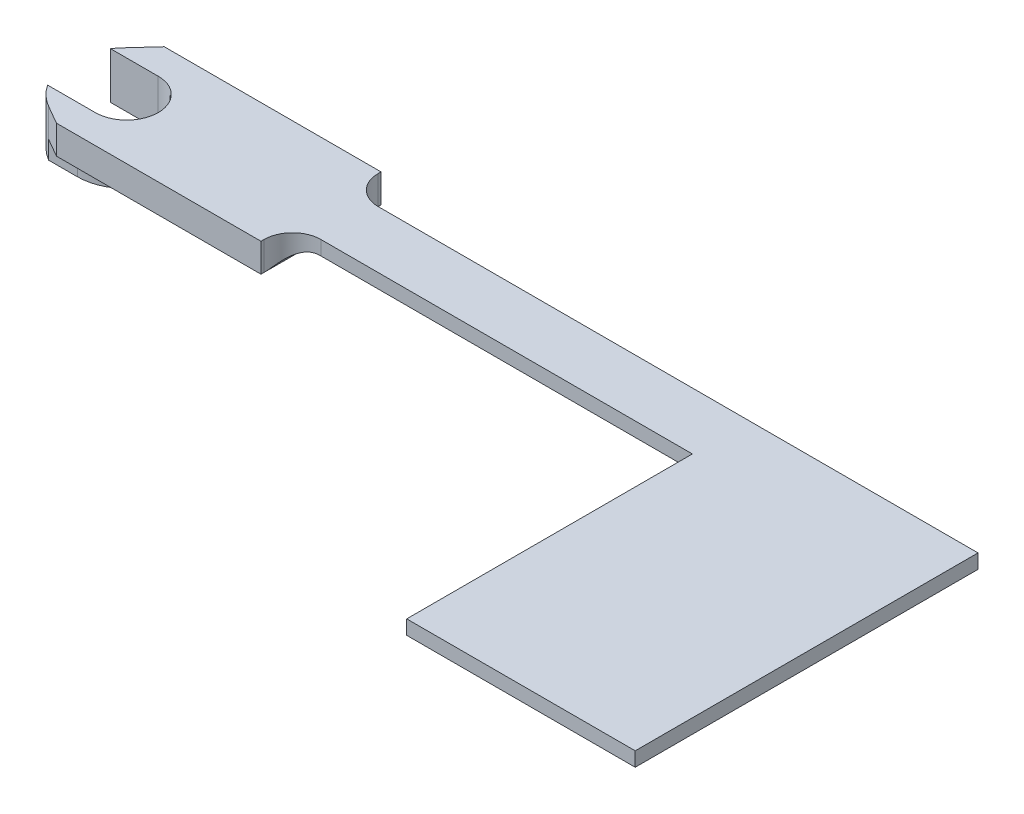
SolidWorks part; units mm, degrees
ref_plane "Front Plane" through (0, 0, 0) normal (0, 0, 1) x (1, 0, 0)
ref_plane "Top Plane" through (0, 0, 0) normal (0, 1, 0) x (1, 0, 0)
ref_plane "Right Plane" through (0, 0, 0) normal (1, 0, 0) x (0, 0, -1)
sketch "Sketch1" plane through (0, 0, 0) normal (0, 1, 0) x (1, 0, 0)
  line L0 (0, 0) -> (27.8118, 30.498) construction
  line L1 (0, 0) -> (41.275, 0) construction
  line L2 (23.296, 15.6137) -> (32.6062, 26.3344)
  line L3 (-4.692, 4.2787) -> (23.1198, 34.7768)
  line L4 (-3.175, -5.4993) -> (27.7812, -23.3719)
  line L5 (41.275, -23.8125) -> (41.275, -26.9875) construction
  line L6 (47.849, -24.5345) -> (47.4381, -23.0011) construction
  line L7 (47.849, -24.5345) -> (48.2599, -26.0679) construction
  circle A4 centre (41.275, 0) radius 19.05 construction
  circle A5 centre (41.275, 0) radius 23.8125
  circle A6 centre (41.275, 0) radius 26.9875
  circle A7 centre (27.8118, 30.498) radius 6.35
  arc A8 (41.275, -26.9875) -> (41.275, -23.8125) centre (41.275, -25.4) ccw construction
  circle A10 centre (0, 0) radius 6.35
  arc A11 (48.2599, -26.0679) -> (47.4381, -23.0011) centre (47.849, -24.5345) ccw
  dimension "D1" = 38.1
  dimension "D4" = 12.7
  dimension "D5" = 3.175
  dimension "D3" = 12.7
  dimension "D6" = 41.275
  dimension "D7" = 15
  dimension "D2" = 4.7625
extrude "Boss-Extrude1" add sketch "Sketch1" along normal blind 4.7625
sketch "Sketch2" plane through (0, 4.7625, 0) normal (0, 1, 0) x (1, 0, 0)
  line L0 (0, 3.5) -> (-5.2983, 3.5)
  line L1 (0, -3.5) -> (-5.2983, -3.5)
  line L2 (1.8028, 3) -> (17.8028, 2)
  line L3 (17.8028, 2) -> (17.8028, -2)
  line L4 (17.8028, -2) -> (1.8028, -3)
  line L5 (1.8028, 3) -> (1.8028, -3) construction
  circle A0 centre (0, 0) radius 3.5
  arc A1 (-4.692, 4.2787) -> (-3.175, -5.4993) centre (0, 0) ccw construction
  arc A2 (-5.2983, 3.5) -> (-5.2983, -3.5) centre (0, 0) ccw
  point P12 (1.8028, 0)
  point P16 (17.8028, 0)
  dimension "D1" = 7
  dimension "D2" = 6
  dimension "D3" = 4
  dimension "D4" = 16
sketch "Sketch5" plane through (0, 0, 0) normal (0, -1, 0) x (1, 0, 0)
  line L0 (0, 3.5) -> (-5.2983, 3.5) construction
  line L1 (0, -3.5) -> (-5.2983, -3.5) construction
  line L2 (0, 3.5) -> (-5.2983, 3.5)
  line L3 (0, -3.5) -> (-5.2983, -3.5)
  circle A0 centre (0, 0) radius 3.5 construction
  circle A1 centre (0, 0) radius 3.5
  arc M1 (-3.175, 5.4993) -> (-4.692, -4.2787) centre (0, 0) ccw
extrude "Cut-Extrude2" cut sketch "Sketch5" against normal offset from surface (3.3712 mm away) 1.3912 contours A1 | A1 L2 L3 M1 up to face at (22.9306, 4.7625, 0.3962)
sketch "Sketch6" plane through (0, 3.3713, 0) normal (0, -1, 0) x (1, 0, 0)
  line L0 (17.8028, -2) -> (17.8028, 2) construction
  line L1 (1.8028, -3) -> (17.8028, -2) construction
  line L2 (17.8028, 2) -> (1.8028, 3) construction
  line L3 (17.8028, -2) -> (17.8028, 2)
  line L4 (1.8028, -3) -> (17.8028, -2)
  line L5 (17.8028, 2) -> (1.8028, 3)
  circle A0 centre (0, 0) radius 3.5 construction
  arc A1 (1.8028, -3) -> (1.8028, 3) centre (0, 0) ccw
extrude "Cut-Extrude3" cut sketch "Sketch6" along normal offset from surface (1.98 mm away) 1.3912 up to face at (14.8799, 0, 0.2432)
sketch "Sketch10" plane through (-3.175, 0, 5.4993) normal (-0.5, 0, 0.866) x (0.866, 0, 0.5)
  line L0 (12.368, 0) -> (15.0706, 0) construction
  line L1 (15.0706, 4.7625) -> (12.368, 4.7625) construction
  line L2 (11.9327, 0) -> (52.5832, 0) construction
  line L3 (52.5832, 4.7625) -> (11.9327, 4.7625) construction
  line L4 (2.6339, 0) -> (15.1867, 0) construction
  line L5 (15.1867, 4.7625) -> (2.6339, 4.7625) construction
  line L6 (2.6339, 0) -> (-6.2028, 0) construction
  line L7 (-6.2028, 4.7625) -> (2.6339, 4.7625) construction
  line L8 (-6.35, 3.3712) -> (-2.8385, 3.3712) construction
  line L9 (-2.8385, 3.3712) -> (-2.8385, 0) construction
  line L10 (-2.8385, 0) -> (0, 0) construction
  line L11 (0, 4.7625) -> (-6.35, 4.7625) construction
  line L12 (-6.3385, 0) -> (-6.2028, 0) construction
  line L13 (-6.3385, 0) -> (-6.3385, 3.3712) construction
  line L14 (0, 0) -> (35.7452, 0) construction
  line L15 (35.7452, 4.7625) -> (0, 4.7625) construction
  line L16 (35.7452, 0) -> (54.8282, 0) construction
  line L17 (54.8282, 4.7625) -> (35.7452, 4.7625) construction
  line L18 (52.5832, 0) -> (55.2932, 0) construction
  line L19 (55.2932, 4.7625) -> (52.5832, 4.7625) construction
  line L20 (12.368, 0) -> (15.0706, 0) construction
  line L21 (15.0706, 4.7625) -> (12.368, 4.7625) construction
  line L22 (11.9327, 0) -> (52.5832, 0) construction
  line L23 (52.5832, 4.7625) -> (11.9327, 4.7625) construction
  line L24 (2.6339, 0) -> (15.1867, 0) construction
  line L25 (15.1867, 4.7625) -> (2.6339, 4.7625) construction
  line L26 (2.6339, 0) -> (-6.2028, 0) construction
  line L27 (-6.2028, 4.7625) -> (2.6339, 4.7625) construction
  line L28 (-6.35, 3.3712) -> (-2.8385, 3.3712) construction
  line L29 (-2.8385, 3.3712) -> (-2.8385, 0) construction
  line L30 (-2.8385, 0) -> (0, 0) construction
  line L31 (0, 4.7625) -> (-6.35, 4.7625) construction
  line L32 (-6.3385, 0) -> (-6.2028, 0) construction
  line L33 (-6.3385, 0) -> (-6.3385, 3.3712) construction
  line L34 (0, 0) -> (35.7452, 0) construction
  line L35 (35.7452, 4.7625) -> (0, 4.7625) construction
  line L36 (35.7452, 0) -> (54.8282, 0) construction
  line L37 (54.8282, 4.7625) -> (35.7452, 4.7625) construction
  line L38 (52.5832, 0) -> (55.2932, 0) construction
  line L39 (55.2932, 4.7625) -> (52.5832, 4.7625) construction
  line L41 (-6.35, 4.7625) -> (55.2932, 4.7625)
  line L42 (-6.35, 4.7625) -> (-6.35, 0)
  line L43 (-6.35, 0) -> (55.2932, 0)
  line L44 (55.2932, 4.7625) -> (55.2932, 0)
  line L45 (-6.35, 3.9688) -> (55.2932, 3.9688)
  line L46 (-6.35, 3.9688) -> (-6.35, 0.7938)
  line L47 (-6.35, 0.7938) -> (55.2932, 0.7938)
  line L48 (55.2932, 3.9688) -> (55.2932, 0.7938)
  point P26 (-6.35, 2.3813)
  line M29 (0, 0) -> (35.7452, 0)
  line M30 (35.7452, 0) -> (35.7452, 4.7625)
  line M31 (35.7452, 4.7625) -> (0, 4.7625)
  line M32 (0, 4.7625) -> (0, 0)
  dimension "D1" = 3.175
  dimension "D2" = 1.5875
extrude "Cut-Extrude4" cut sketch "Sketch10" against normal through all contours L42 L45 L41 M32 | L45 M32 M30 M31 | L45 L44 L41 M30 | L47 L43 L44 M30 | L47 M32 M29 M30 | L47 L42 L43 M32
sketch "Sketch11" plane through (0, 3.3713, 0) normal (0, -1, 0) x (1, 0, 0)
  line L0 (-5.2983, 3.5) -> (0, 3.5) construction
  line L1 (-5.2983, -3.5) -> (0, -3.5) construction
  line L2 (-5.2983, 3.5) -> (0, 3.5)
  line L3 (-5.2983, -3.5) -> (0, -3.5)
  arc A0 (-5.2983, 3.5) -> (-5.2983, -3.5) centre (0, 0) ccw construction
  arc A1 (0, -3.5) -> (0, 3.5) centre (0, 0) ccw construction
  arc A2 (-5.2983, 3.5) -> (-5.2983, -3.5) centre (0, 0) ccw
  arc A3 (0, -3.5) -> (0, 3.5) centre (0, 0) ccw
extrude "Cut-Extrude5" cut sketch "Sketch11" against normal blind 2.54
sketch "Sketch12" plane through (0, 0.7938, 0) normal (0, -1, 0) x (1, 0, 0)
  line L0 (-3.175, 5.4993) -> (27.7812, 23.3719) construction
  line L1 (23.1198, -34.7768) -> (-4.692, -4.2787) construction
  line L2 (-5.2983, 3.5) -> (0, 3.5) construction
  line L3 (-5.2983, -3.5) -> (0, -3.5) construction
  line L4 (-3.175, 5.4993) -> (-3.1737, 5.5)
  line L5 (-3.5783, -5.5) -> (-4.692, -4.2787)
  line L6 (-5.2983, 3.5) -> (0, 3.5)
  line L7 (-5.2983, -3.5) -> (0, -3.5)
  line L8 (-3.5783, -5.5) -> (0, -5.5)
  line L9 (-3.1737, 5.5) -> (0, 5.5)
  line L10 (-5.2983, -5.5) -> (0, -5.5) construction
  line L11 (-5.2983, 5.5) -> (0, 5.5) construction
  arc A0 (-5.2983, -3.5) -> (-4.692, -4.2787) centre (0, 0) ccw construction
  arc A1 (-3.175, 5.4993) -> (-5.2983, 3.5) centre (0, 0) ccw construction
  arc A2 (0, -3.5) -> (0, 3.5) centre (0, 0) ccw construction
  arc A3 (-5.2983, -3.5) -> (-4.692, -4.2787) centre (0, 0) ccw
  arc A4 (-3.175, 5.4993) -> (-5.2983, 3.5) centre (0, 0) ccw
  arc A5 (0, -3.5) -> (0, 3.5) centre (0, 0) ccw
  arc A6 (0, -5.5) -> (0, 5.5) centre (0, 0) ccw
  dimension "D1" = 2
extrude "Boss-Extrude2" add sketch "Sketch12" along normal blind 2
sketch "Sketch14" plane through (0, 3.9688, 0) normal (0, 1, 0) x (1, 0, 0)
  line L0 (0, -3.5) -> (-5.2983, -3.5) construction
  line L1 (-5.2983, 3.5) -> (17.7211, 3.5)
  line L2 (1.8028, -3) -> (17.548, -2.0159)
  line L3 (17.548, 2.0159) -> (1.8028, 3)
  line L4 (1.8028, -3) -> (17.548, -2.0159)
  line L5 (17.548, 2.0159) -> (1.8028, 3)
  line L6 (-5.2983, 3.5) -> (-5.2983, -3.5)
  line L7 (-5.2983, -3.5) -> (17.7211, -3.5)
  line L8 (17.7211, 3.5) -> (17.7211, -3.5)
  line L9 (-8.4733, 6.675) -> (20.8961, 6.675)
  line L10 (20.8961, 6.675) -> (20.8961, -6.675)
  line L11 (-8.4733, -6.675) -> (20.8961, -6.675)
  line L12 (-8.4733, 6.675) -> (-8.4733, -6.675)
  line L13 (-5.2983, 3.5) -> (-5.2983, 6.675)
  line L14 (-5.2983, -3.5) -> (-5.2983, -6.675)
  arc A0 (23.296, 15.6137) -> (47.4381, -23.0011) centre (41.275, 0) ccw construction
  arc A1 (23.296, 15.6137) -> (47.4381, -23.0011) centre (41.275, 0) ccw
  arc A2 (1.8028, -3) -> (1.8028, 3) centre (0, 0) ccw
  arc A3 (17.548, 2.0159) -> (17.548, -2.0159) centre (41.275, 0) ccw
  arc A4 (1.8028, -3) -> (1.8028, 3) centre (0, 0) ccw
  arc A5 (17.548, 2.0159) -> (17.548, -2.0159) centre (41.275, 0) ccw
  line M16 (-3.175, -5.4993) -> (27.7812, -23.3719)
  arc M17 (27.7812, -23.3719) -> (48.2599, -26.0679) centre (41.275, 0) ccw
  arc M18 (48.2599, -26.0679) -> (47.4381, -23.0011) centre (47.849, -24.5345) ccw
  arc M19 (47.4381, -23.0011) -> (23.296, 15.6137) centre (41.275, 0) cw
  line M20 (23.296, 15.6137) -> (32.6062, 26.3344)
  arc M21 (32.6062, 26.3344) -> (23.1198, 34.7768) centre (27.8118, 30.498) ccw
  line M22 (23.1198, 34.7768) -> (-4.692, 4.2787)
  dimension "D1" = 0
  dimension "D2" = 3.175
extrude "Cut-Extrude6" cut sketch "Sketch14" against normal through all contours L9 M22 M19 M20 M21 | L11 M16 M17 M18 M19
ref_plane "Plane1" through (18.4172, 0, 0) normal (1, 0, 0) x (0, 0, -1)
sketch "Sketch15" plane through (18.4172, 0, 0) normal (1, 0, 0) x (0, 0, -1)
  line L0 (2.0159, 1.3913) -> (-2.0159, 1.3913) construction
  line L1 (-2.0159, 1.3913) -> (-2.0159, 3.3713) construction
  line L2 (-2.0159, 3.3713) -> (2.0159, 3.3713) construction
  line L3 (2.0159, 3.3713) -> (2.0159, 1.3913) construction
  line L4 (6.675, 0.7938) -> (6.675, 3.9688)
  line L5 (6.675, 3.9688) -> (-6.675, 3.9688)
  line L6 (-6.675, 3.9688) -> (-6.675, 0.7938)
  line L7 (-6.675, 0.7938) -> (6.675, 0.7938)
  line L8 (6.675, 0.7938) -> (6.675, 3.9688)
  line L9 (6.675, 3.9688) -> (-6.675, 3.9688)
  line L10 (-6.675, 3.9688) -> (-6.675, 0.7938)
  line L11 (-6.675, 0.7938) -> (6.675, 0.7938)
  line L12 (2.0159, 1.3913) -> (-2.0159, 1.3913)
  line L13 (-2.0159, 1.3913) -> (-2.0159, 3.3713)
  line L14 (-2.0159, 3.3713) -> (2.0159, 3.3713)
  line L15 (2.0159, 3.3713) -> (2.0159, 1.3913)
  dimension "D1" = 0
extrude "Boss-Extrude4" add sketch "Sketch15" against normal up to next
sketch "Sketch20" plane through (18.4172, 0, 0) normal (1, 0, 0) x (0, 0, -1)
  line L4 (-6.675, 0.7938) -> (6.675, 0.7938)
  line L5 (6.675, 0.7938) -> (6.675, 3.9688)
  line L6 (6.675, 3.9688) -> (-6.675, 3.9688)
  line L7 (-6.675, 3.9688) -> (-6.675, 0.7938)
  line L8 (-6.675, 0.7938) -> (6.675, 0.7938)
  line L9 (6.675, 0.7938) -> (6.675, 3.9688)
  line L10 (6.675, 3.9688) -> (-6.675, 3.9688)
  line L11 (-6.675, 3.9688) -> (-6.675, 0.7938)
  dimension "D1" = 0
extrude "Boss-Extrude7" add sketch "Sketch20" along normal blind 3.175
sketch "Sketch21" plane through (0, 3.9688, 0) normal (0, 1, 0) x (1, 0, 0)
  line L0 (21.5922, 6.675) -> (21.5922, -6.675) construction
  line L1 (21.5922, 3.175) -> (91.4422, 3.175)
  line L2 (21.5922, 3.175) -> (21.5922, -3.175)
  line L3 (21.5922, -3.175) -> (91.4422, -3.175)
  line L4 (91.4422, 3.175) -> (91.4422, -3.175)
  line L6 (91.4422, -3.175) -> (66.0422, -3.175)
  line L7 (91.4422, -3.175) -> (91.4422, -34.925)
  line L8 (91.4422, -34.925) -> (66.0422, -34.925)
  line L9 (66.0422, -3.175) -> (66.0422, -34.925)
  point P9 (21.5922, 0)
  line M10 (21.5922, -6.675) -> (21.5922, 6.675)
  dimension "D1" = 6.35
  dimension "D2" = 25.4
  dimension "D3" = 69.85
  dimension "D4" = 38.1
extrude "Boss-Extrude8" add sketch "Sketch21" against normal blind 1.5875 contours L3 L9 L8 L7 | L4 L1 L3 M10
fillet "Fillet1" radius 3.175 3 edges at (21.5922, 3.175, -3.175) (21.5922, 2.3813, 0) (21.5922, 3.175, 3.175)
